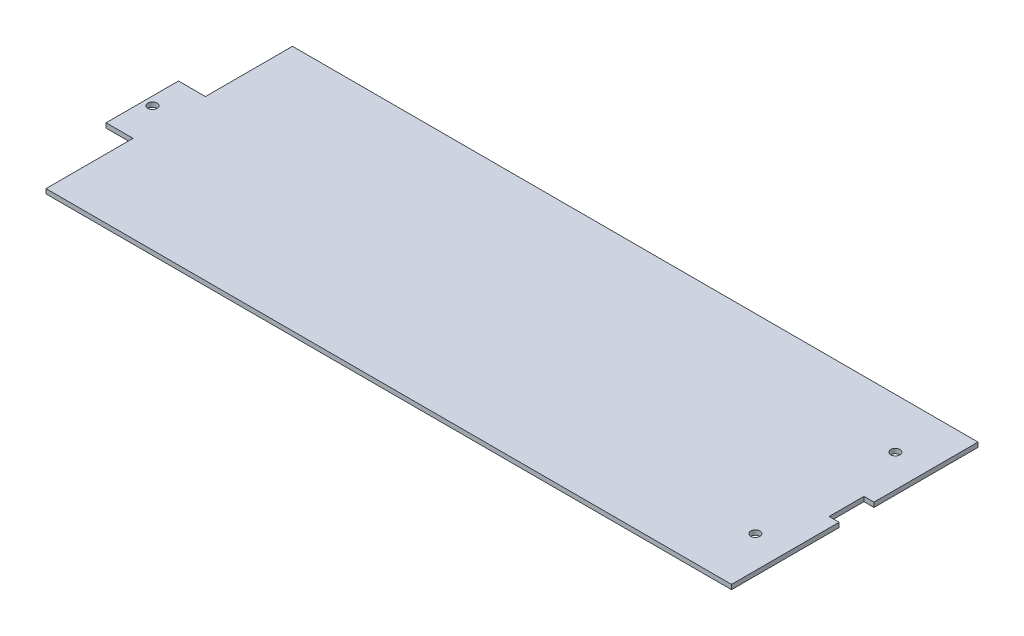
SolidWorks part; units mm, degrees
ref_plane "Front Plane" through (0, 0, 0) normal (0, 0, 1) x (1, 0, 0)
ref_plane "Top Plane" through (0, 0, 0) normal (0, 1, 0) x (1, 0, 0)
ref_plane "Right Plane" through (0, 0, 0) normal (1, 0, 0) x (0, 0, -1)
sketch "Sketch1" plane through (0, 0, 0) normal (0, 1, 0) x (1, 0, 0)
  line L0 (-302.2355, -559.9723) -> (-284.7355, -559.9723)
  line L1 (-284.7355, -503.4723) -> (160.2645, -503.4723)
  line L2 (-284.7355, -503.4723) -> (-284.7355, -559.9723)
  line L5 (-296.7465, -657.2402) -> (-296.7465, -507.3802) construction
  line L6 (-284.7355, -503.4723) -> (-286.6881, -517.4386) construction
  line L7 (-302.2355, -559.9723) -> (-302.2355, -606.9723)
  line L8 (-302.2355, -606.9723) -> (-284.7355, -606.9723)
  line L9 (-284.7355, -606.9723) -> (-284.7355, -663.4723)
  line L10 (-284.7355, 31.0446) -> (-284.7355, -559.9723) construction
  line L11 (160.2645, -503.4723) -> (160.2645, -571.0102)
  line L12 (160.2645, -571.0102) -> (153.7645, -571.0102)
  line L13 (-302.2355, -583.4723) -> (-26.2365, -582.3102) construction
  line L14 (161.6735, -574.0102) -> (169.6735, -574.0102) construction
  line L15 (153.7645, -571.0102) -> (153.7645, -593.6102)
  line L16 (153.7645, -593.6102) -> (160.2645, -593.6102)
  line L17 (169.6735, -590.6102) -> (161.6735, -590.6102) construction
  line L18 (160.2645, -593.6102) -> (160.2645, -663.4723)
  line L19 (160.2645, -663.4723) -> (-284.7355, -663.4723)
  line L20 (-194.7355, 72.7736) -> (70.2645, 72.7736) construction
  line L21 (-184.7355, -707.4612) -> (-284.7355, -707.4612) construction
  line L22 (-62.2355, -503.4723) -> (-62.2355, -738.3845) construction
  circle A0 centre (-296.7465, -582.3102) radius 3
  circle A1 centre (-194.7355, 72.7736) radius 3
  circle A2 centre (70.2645, 72.7736) radius 3.5
  circle A3 centre (75.7774, -1236.5582) radius 3.5
  circle A4 centre (-189.2132, -1238.7897) radius 3
  circle A5 centre (139.1024, -535.9723) radius 3
  circle A6 centre (139.4867, -627.2542) radius 3
  circle A7 centre (-184.7355, -707.4612) radius 3
  circle A8 centre (60.2645, -707.4612) radius 3
  circle A9 centre (59.2075, -456.4352) radius 3
  circle A10 centre (-185.7838, -458.4983) radius 3
  point P4 (0, 0)
  dimension "D9" = 6.5
  dimension "D12" = 6
  dimension "D3" = 6
  dimension "D15" = 6
  dimension "D16" = 7
  dimension "D18" = 6
  dimension "D1" = 56.5
  dimension "D2" = 56.5
  dimension "D4" = 3
  dimension "D5" = 3
  dimension "D6" = 17.5
  dimension "D7" = 445
  dimension "D8" = 69.8621
  dimension "D10" = 160
  dimension "D11" = 67.5379
  dimension "D13" = 90
  dimension "D14" = 90
  dimension "D17" = 32.5
  dimension "D19" = 100
extrude "Boss-Extrude1" add sketch "Sketch1" along normal blind 3 from offset 2 contours L8 L9 L1 L2 L0 L7 region at (-65.4, 0, 583.4766)
